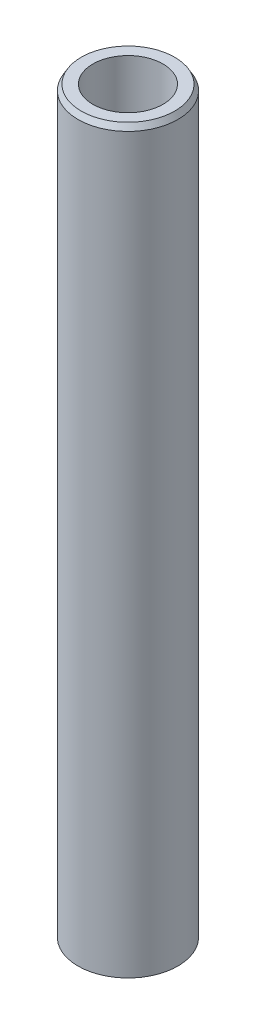
SolidWorks part; units mm, degrees
ref_plane "Front Plane" through (0, 0, 0) normal (0, 0, 1) x (1, 0, 0)
ref_plane "Top Plane" through (0, 0, 0) normal (0, 1, 0) x (1, 0, 0)
ref_plane "Right Plane" through (0, 0, 0) normal (1, 0, 0) x (0, 0, -1)
sketch "Sketch1" plane through (0, 0, 0) normal (0, 1, 0) x (1, 0, 0)
  circle A0 centre (0, 0) radius 15
  dimension "SHAFT_OD" = 30
extrude "Boss-Extrude1" add sketch "Sketch1" along normal blind 222.7413
sketch "Sketch2" plane through (0, 0, 0) normal (0, 1, 0) x (1, 0, 0)
  circle A0 centre (0, 0) radius 10.5196
  dimension "BORE_D" = 21.0392
extrude "Cut-Extrude1" cut sketch "Sketch2" along normal through all
chamfer "Chamfer1" distance 1.6898 angle 30 2 edges at (0, 222.7413, 15) (0, 0, 15) first distance on face at (0, 222.7413, 15) first distance on face at (0, 0, 10.5196)
